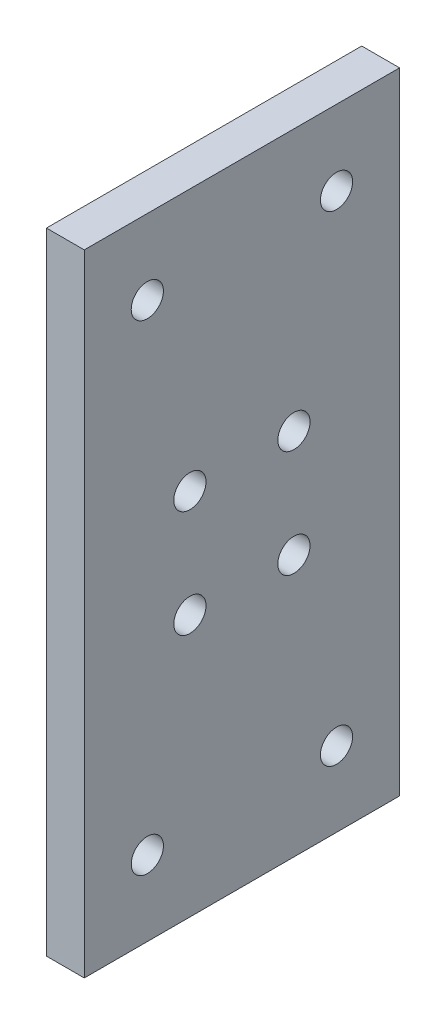
SolidWorks part; units mm, degrees
ref_plane "Front Plane" through (0, 0, 0) normal (1, 0, 0) x (0, 1, 0)
ref_plane "Top Plane" through (0, 0, 0) normal (0, 0, 1) x (0, 1, 0)
ref_plane "Right Plane" through (0, 0, 0) normal (0, 1, 0) x (-1, 0, 0)
sketch "Sketch1" plane through (0, 0, 0) normal (1, 0, 0) x (0, 1, 0)
  line L0 (0, 25) -> (0, -25) construction
  line L1 (-50, -25) -> (50, -25)
  line L2 (-50, -25) -> (-50, 25)
  line L3 (-50, 25) -> (50, 25)
  line L4 (50, -25) -> (50, 25)
  line L5 (-50, -25) -> (50, 25) construction
  line L6 (-50, 25) -> (50, -25) construction
  line L8 (-8.5, -8.25) -> (8.5, -8.25) construction
  line L9 (-8.5, -8.25) -> (-8.5, 8.25) construction
  line L10 (-8.5, 8.25) -> (8.5, 8.25) construction
  line L11 (8.5, -8.25) -> (8.5, 8.25) construction
  line L12 (-8.5, -8.25) -> (8.5, 8.25) construction
  line L13 (-8.5, 8.25) -> (8.5, -8.25) construction
  line L14 (-38.1, -15) -> (38.1, -15) construction
  line L15 (-38.1, -15) -> (-38.1, 15) construction
  line L16 (-38.1, 15) -> (38.1, 15) construction
  line L17 (38.1, -15) -> (38.1, 15) construction
  line L18 (-38.1, -15) -> (38.1, 15) construction
  line L19 (-38.1, 15) -> (38.1, -15) construction
  circle A0 centre (-8.5, 8.25) radius 2.555
  circle A1 centre (-8.5, -8.25) radius 2.555
  circle A2 centre (8.5, -8.25) radius 2.555
  circle A3 centre (8.5, 8.25) radius 2.555
  circle A4 centre (-38.1, 15) radius 2.555
  circle A5 centre (-38.1, -15) radius 2.555
  circle A6 centre (38.1, 15) radius 2.555
  circle A7 centre (38.1, -15) radius 2.555
  point P0 (0, 0)
  point P8 (0, 0)
  point P17 (0, 0)
  dimension "D5" = 5.11
  dimension "D6" = 5.11
  dimension "D9" = 5.11
  dimension "D10" = 5.11
  dimension "D1" = 16.5
  dimension "D2" = 17
  dimension "D3" = 100
  dimension "D4" = 50
  dimension "D7" = 76.2
  dimension "D8" = 30
extrude "Boss-Extrude1" add sketch "Sketch1" along normal blind 6
